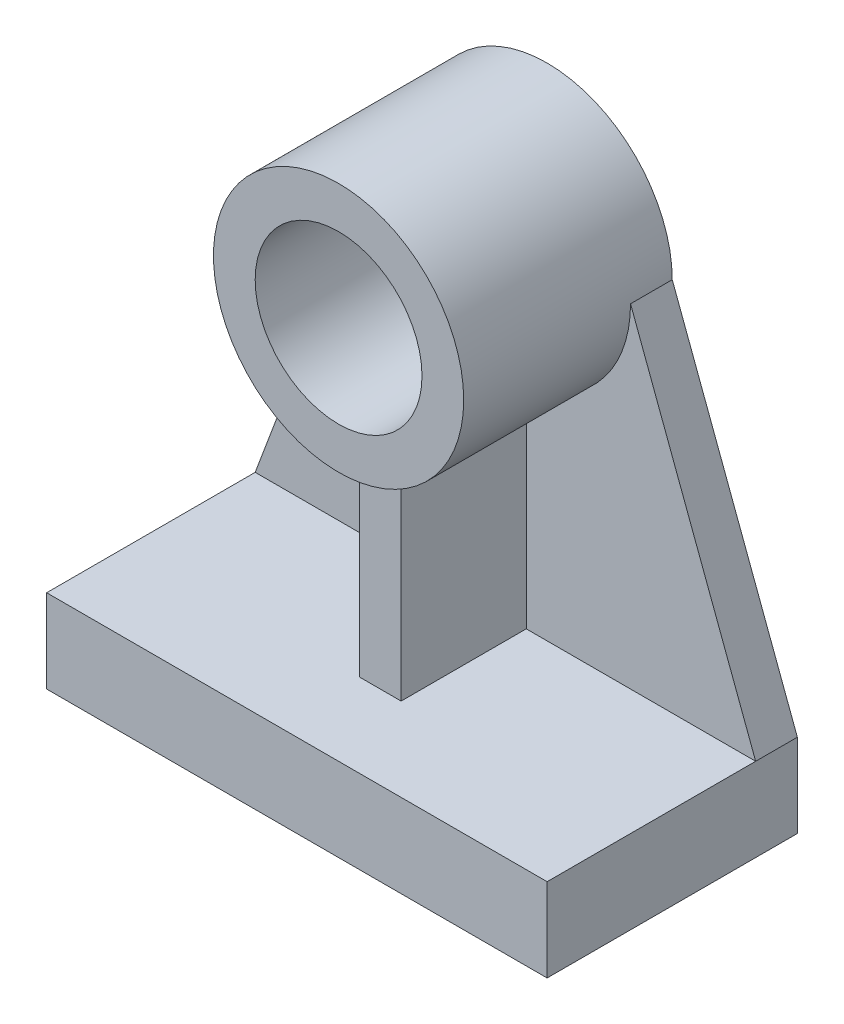
SolidWorks part; units mm, degrees
material "6063-T6"
ref_plane "Front Plane" through (0, 0, 0) normal (0, 0, 1) x (1, 0, 0)
ref_plane "Top Plane" through (0, 0, 0) normal (0, 1, 0) x (1, 0, 0)
ref_plane "Right Plane" through (0, 0, 0) normal (1, 0, 0) x (0, 0, -1)
sketch "Sketch2" plane through (0, 0, 0) normal (0, 0, 1) x (1, 0, 0)
  line L0 (-76.2, 0) -> (-152.4, -203.2)
  line L1 (-152.4, -254) -> (152.4, -254)
  line L2 (-152.4, -254) -> (-152.4, -203.2)
  line L3 (-152.4, -203.2) -> (152.4, -203.2)
  line L4 (152.4, -254) -> (152.4, -203.2)
  line L6 (-12.7, -203.2) -> (-12.7, -75.1342)
  line L8 (12.7, -203.2) -> (12.7, -75.1342)
  line L9 (76.2, 0) -> (152.4, -203.2)
  circle A0 centre (0, 0) radius 50.8
  circle A1 centre (0, 0) radius 76.2
  point P4 (0, -254)
  point P5 (152.4, -254)
  point P6 (-152.4, -254)
  point P7 (-152.4, -203.2)
  point P8 (152.4, -203.2)
  point P9 (0, -203.2)
  point P10 (12.7, -203.2)
  point P11 (-12.7, -203.2)
  point P12 (0, 0)
  dimension "D1" = 101.6
  dimension "D2" = 152.4
  dimension "D3" = 12.7
  dimension "D4" = 152.4
  dimension "D5" = 203.2
extrude "Boss-Extrude7" add sketch "Sketch2" along normal blind 127 contours A1 A0 region at (0, 74.0447, 0)
extrude "Boss-Extrude8" add sketch "Sketch2<11>" along normal blind 101.6 contours A1 L6 L3 L8 region at (0, -139.5225, 0)
sketch "Sketch2<11>" plane through (0, 0, 0) normal (0, 0, 1) x (1, 0, 0) same geometry as "Sketch2"
extrude "Boss-Extrude9" add sketch "Sketch2<12>" along normal blind 152.4 contours L1 L4 L3 L2 region at (0, -228.6, 0)
sketch "Sketch2<12>" plane through (0, 0, 0) normal (0, 0, 1) x (1, 0, 0) same geometry as "Sketch2"
extrude "Boss-Extrude10" add sketch "Sketch2<13>" along normal blind 25.4 contours A1 L0 L3 L6 | A1 L8 L3 L9 region at (-71.4891, -131.909, 0) region at (71.4891, -131.909, 0)
sketch "Sketch2<13>" plane through (0, 0, 0) normal (0, 0, 1) x (1, 0, 0) same geometry as "Sketch2"
